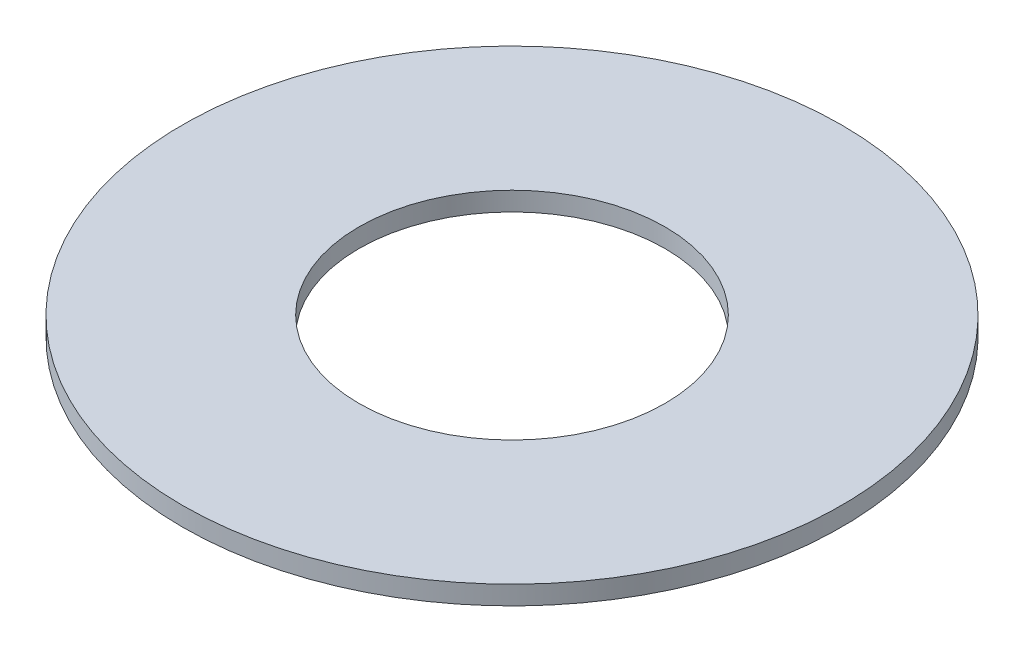
SolidWorks part; units mm, degrees
ref_plane "Front Plane" through (0, 0, 0) normal (0, 0, 1) x (1, 0, 0)
ref_plane "Top Plane" through (0, 0, 0) normal (0, 1, 0) x (1, 0, 0)
ref_plane "Right Plane" through (0, 0, 0) normal (1, 0, 0) x (0, 0, -1)
sketch "Sketch1" plane through (0, 0, 0) normal (0, 1, 0) x (1, 0, 0)
  circle A0 centre (0, 0) radius 70
  dimension "FLANGE_OD" = 140
extrude "Boss-Extrude1" add sketch "Sketch1" along normal blind 4
sketch "Sketch2" plane through (0, 0, 0) normal (0, 1, 0) x (1, 0, 0)
  circle A0 centre (0, 0) radius 32.5
  dimension "BORE_D" = 65
extrude "Cut-Extrude1" cut sketch "Sketch2" along normal through all
sketch "Sketch3" plane through (0, 4, 0) normal (0, 1, 0) x (1, 0, 0)
  circle A0 centre (0, 0) radius 24.8675 construction
  circle A1 centre (-24.8675, 0) radius 5.0291
  dimension "BOLT_D" = 10.0582
  dimension "BOLT_PCD" = 49.735
extrude "Cut-Extrude2" cut sketch "Sketch3" against normal blind 3.9398 rebuild error yes
pattern_circular "CirPattern1" count 3 over 360 rebuild error yes
